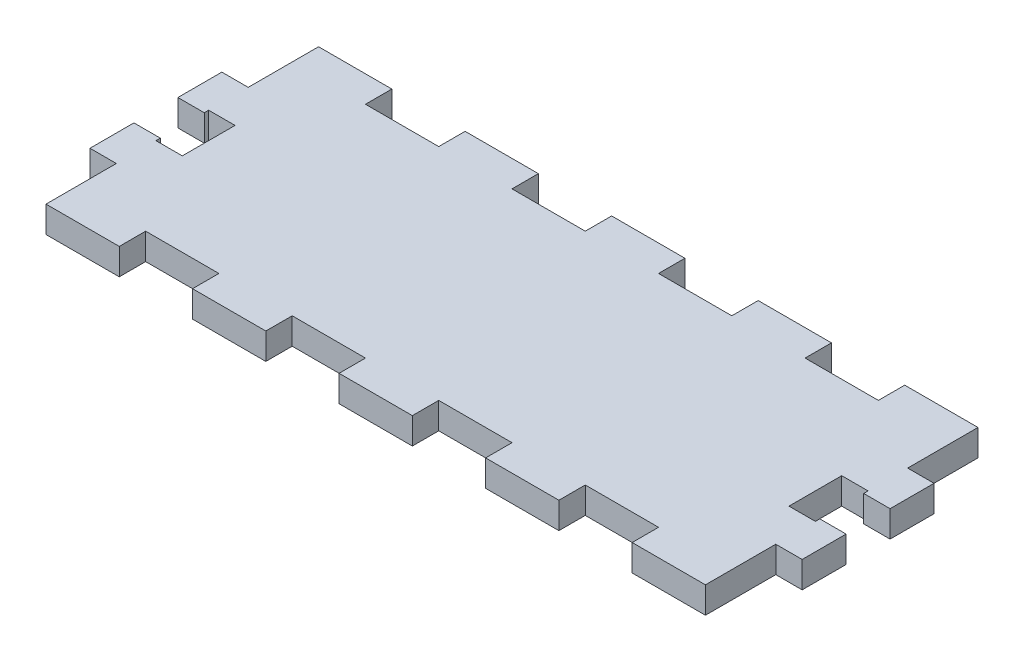
SolidWorks part; units mm, degrees
ref_plane "Front Plane" through (0, 0, 0) normal (0, 0, 1) x (1, 0, 0)
ref_plane "Top Plane" through (0, 0, 0) normal (0, 1, 0) x (1, 0, 0)
ref_plane "Right Plane" through (0, 0, 0) normal (1, 0, 0) x (0, 0, -1)
sketch "Sketch1" plane through (0, 0, 0) normal (0, 1, 0) x (1, 0, 0)
  line L1 (-81, 31) -> (81, 31)
  line L2 (-81, 31) -> (-81, -31)
  line L3 (-81, -31) -> (81, -31)
  line L4 (81, 31) -> (81, -31)
  line L5 (-81, 31) -> (81, -31) construction
  line L6 (-81, -31) -> (81, 31) construction
  point P0 (0, 0)
  dimension "D1" = 162
  dimension "D2" = 62
sketch "Sketch2" plane through (0, 0, 0) normal (0, 0, 1) x (1, 0, 0)
  line L0 (0, 0) -> (0, 6) construction
  line L1 (-81, 0) -> (81, 0) construction
extrude "Boss-Extrude1" add sketch "Sketch1" along normal up to vertex (6 mm away) contours L2 L3 L4 L1 up to point (0, 6, 0)
sketch "Sketch3" plane through (0, 0, 0) normal (0, -1, 0) x (-1, 0, 0)
  line L0 (81, 31) -> (81, -31) construction
  line L1 (75, 15) -> (81, 15)
  line L2 (75, 15) -> (75, 31)
  line L3 (75, 31) -> (81, 31)
  line L4 (81, 15) -> (81, 31)
  line L5 (75, -15) -> (81, -15)
  line L6 (75, -15) -> (75, -31)
  line L7 (75, -31) -> (81, -31)
  line L8 (81, -15) -> (81, -31)
  line L9 (81, -5) -> (75, -5)
  line L10 (81, -5) -> (81, 5)
  line L11 (81, 5) -> (75, 5)
  line L12 (75, -5) -> (75, 5)
  line L13 (81, -5) -> (75, -5) construction
  line L14 (75, -6) -> (75, 6) construction
  line L15 (69, 6) -> (75, 6)
  line L16 (69, 6) -> (69, -6)
  line L17 (69, -6) -> (75, -6)
  line L18 (75, 6) -> (75, -6)
  line L19 (75, -6) -> (69, -6) construction
  line M1 (81, 31) -> (-81, 31)
  line M3 (-81, -31) -> (81, -31)
  line M4 (81, -31) -> (81, 31)
extrude "Cut-Extrude1" cut sketch "Sketch3" against normal through all contours L5 L6 M3 M4 | L12 L9 L11 M4 | L18 L15 L16 L17 L12 | L2 L1 M4 M1 region at (-78, 0, -23) region at (-78, 0, 23) region at (-78, 0, 0) region at (-72, 0, 0)
sketch "Sketch4" plane through (0, 0, 0) normal (0, -1, 0) x (1, 0, 0)
  line L0 (-75, -31) -> (81, -31) construction
  line L1 (-58.3333, -25) -> (-41.6667, -25)
  line L2 (-58.3333, -25) -> (-58.3333, -31)
  line L3 (-58.3333, -31) -> (-41.6667, -31)
  line L4 (-41.6667, -25) -> (-41.6667, -31)
  line L5 (-8.3333, -25) -> (-8.3333, -31) construction
  line L6 (-25, -25) -> (-8.3333, -25)
  line L7 (-25, -25) -> (-25, -31)
  line L8 (-25, -31) -> (-8.3333, -31)
  line L9 (-8.3333, -25) -> (-8.3333, -31)
  line L10 (-41.6667, -25) -> (-41.6667, -31) construction
  point P14 (-41.6667, -28.2)
extrude "Cut-Extrude2" cut sketch "Sketch4" against normal through all
mirror "Mirror1" about plane through (0, 0, 0) normal (0, 0, 1) of "Cut-Extrude2"
mirror "Mirror2" about plane through (0, 0, 0) normal (1, 0, 0) of "Cut-Extrude1", "Mirror1"
equation "\"glass_width\"= 150"
equation "\"glass_height\"= 100"
equation "\"glass_thickness\"= 4"
equation "\"brood_space\"= 42"
equation "\"t1\"= 6"
equation "\"t2\"= 6"
equation "\"box_depth\"= \"brood_space\" + \"glass_thickness\" + \"glass_thickness\" + \"t2\" + \"t2\""
equation "\"box_width\"= \"glass_width\" + \"t1\" + \"t1\""
equation "\"food_height\"= 70"
equation "\"box_height\"= \"glass_height\" + ( \"t1\" * 3 ) + \"food_height\""
equation "\"D1@Sketch1\"=\"box_width\""
equation "\"D1@Sketch2\"=\"t1\""
equation "\"D2@Sketch1\"=\"box_depth\""
equation "\"entry_height\"= 24"
equation "\"entry_diameter\"= 8"
equation "\"food_top_clearance\"= 10"
equation "\"bar_width\"= 20"
equation "\"glassblocker_lower_height\"= 10"
equation "\"lower_edge_stickout\"=6"
